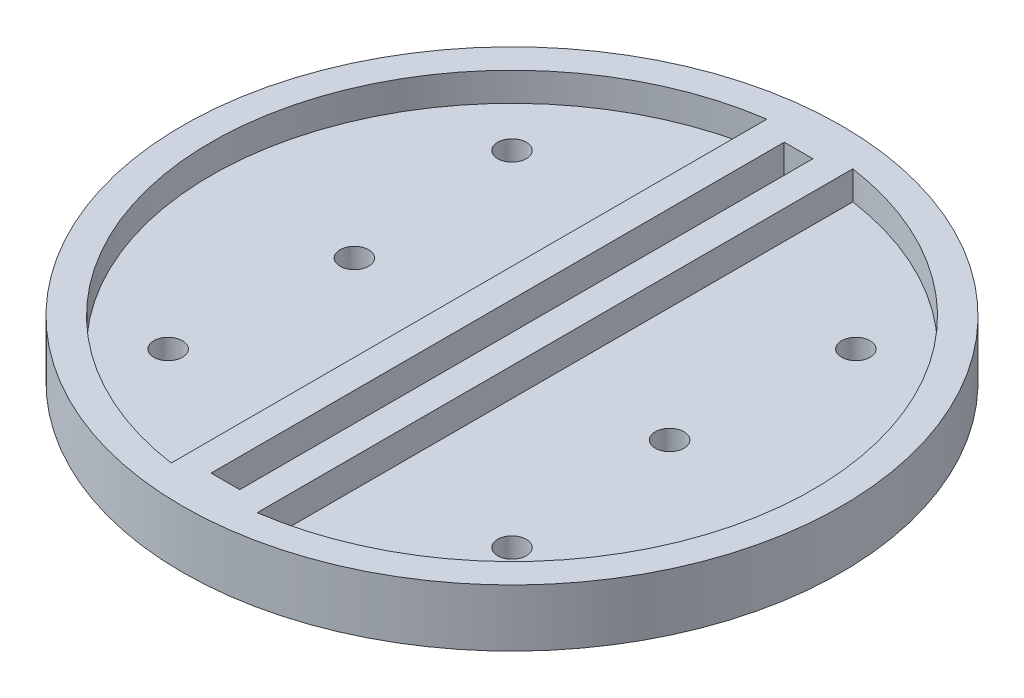
SolidWorks part; units mm, degrees
material "ABS"
ref_plane "Front Plane" through (0, 0, 0) normal (0, 0, 1) x (1, 0, 0)
ref_plane "Top Plane" through (0, 0, 0) normal (0, 1, 0) x (1, 0, 0)
ref_plane "Right Plane" through (0, 0, 0) normal (1, 0, 0) x (0, 0, -1)
sketch "Sketch5" plane through (0, 0, 0) normal (0, 1, 0) x (1, 0, 0)
  circle A0 centre (0, 0) radius 73.025
  circle A1 centre (38.1, 38.1) radius 3.175
  circle A2 centre (38.1, -38.1) radius 3.175
  circle A3 centre (-38.1, 38.1) radius 3.175
  circle A4 centre (-38.1, -38.1) radius 3.175
extrude "PlateBase" add sketch "Sketch5" along normal blind 6.35
sketch "Sketch6" plane through (0, 6.35, 0) normal (0, 1, 0) x (1, 0, 0)
  line L1 (3.175, 0) -> (3.175, 72.9559)
  line L3 (3.175, 0) -> (3.175, -72.9559)
  line L4 (0, 0) -> (3.175, 0)
  line L5 (-3.175, 0) -> (-3.175, 72.9559)
  line L6 (-9.525, 0) -> (-9.525, 72.4011)
  line L7 (-9.525, 0) -> (-9.525, -72.4011)
  line L8 (-3.175, 0) -> (-3.175, -72.9559)
  line L9 (9.525, 0) -> (9.525, 72.4011)
  line L10 (9.525, 0) -> (9.525, -72.4011)
  circle A0 centre (0, 0) radius 73.025 construction
  circle M4 centre (0, 0) radius 73.025
extrude "PlateTop" add sketch "Sketch6" along normal blind 6.35 contours L8 L5 L6 L7 M4 | L10 L9 L1 L3 M4 region at (6.346, 6.35, 0) region at (-6.346, 6.35, 0)
sketch "Sketch9" plane through (0, 6.35, 0) normal (0, 1, 0) x (1, 0, 0)
  circle A0 centre (0, 0) radius 66.675
  circle A1 centre (0, 0) radius 73.025
extrude "PlateWalls" add sketch "Sketch9" along normal blind 6.35
sketch "Sketch13" plane through (0, 6.35, 0) normal (0, 1, 0) x (1, 0, 0)
  circle A0 centre (34.925, 0) radius 3.175
extrude "RightThruHole" cut sketch "Sketch13" against normal blind 6.35
sketch "Sketch14" plane through (0, 6.35, 0) normal (0, 1, 0) x (1, 0, 0)
  circle A0 centre (-34.925, 0) radius 3.175
extrude "LeftThruHole" cut sketch "Sketch14" against normal blind 6.35
sketch "Sketch15" plane through (0, 6.35, 0) normal (0, 1, 0) x (1, 0, 0)
  line L1 (-3.175, 66.5994) -> (-3.175, -66.5994) construction
  line L2 (-3.175, 63.5) -> (3.175, 63.5)
  line L3 (3.175, -66.5994) -> (3.175, 66.5994) construction
  line L4 (3.175, 63.5) -> (3.175, 66.5994)
  line L5 (-3.175, 66.5994) -> (-3.175, 63.5)
  line L7 (-3.175, -63.5) -> (-3.175, -66.5994)
  line L8 (-3.175, -63.5) -> (3.175, -63.5)
  line L9 (3.175, -63.5) -> (3.175, -66.5994)
  arc A0 (3.175, 66.5994) -> (-3.175, 66.5994) centre (0, 0) ccw construction
  arc A1 (3.175, 66.5994) -> (-3.175, 66.5994) centre (0, 0) ccw construction
  arc A2 (-3.175, 66.5994) -> (3.175, 66.5994) centre (0, 0) cw
  arc A3 (-3.175, -66.5994) -> (3.175, -66.5994) centre (0, 0) ccw
extrude "Boss-Extrude1" add sketch "Sketch15" along normal blind 6.35 from surface starting at face at (0, 6.35, 0)
